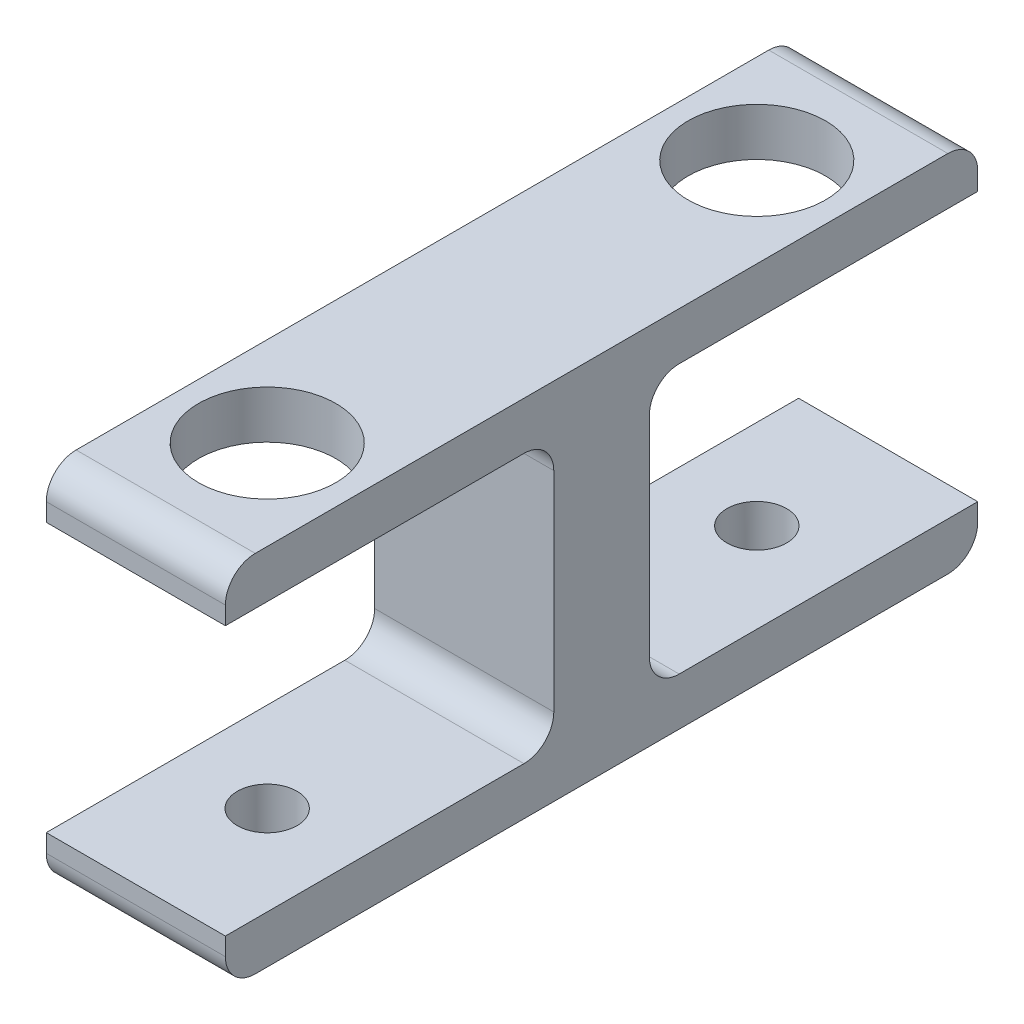
SolidWorks part; units mm, degrees
ref_plane "Front Plane" through (0, 0, 0) normal (0, 0, 1) x (1, 0, 0)
ref_plane "Top Plane" through (0, 0, 0) normal (0, 1, 0) x (1, 0, 0)
ref_plane "Right Plane" through (0, 0, 0) normal (1, 0, 0) x (0, 0, -1)
sketch "Sketch1" plane through (0, 0, 0) normal (1, 0, 0) x (0, 0, -1)
  line L0 (0, 0) -> (55, 0)
  line L1 (55, 0) -> (55, -45)
  line L2 (55, -45) -> (0, -45)
  line L3 (0, -45) -> (0, -53)
  line L4 (0, -53) -> (63, -53)
  line L5 (63, -53) -> (63, 8)
  line L6 (63, 8) -> (0, 8)
  line L7 (0, 8) -> (0, 0)
  dimension "D1" = 55
  dimension "D2" = 45
  dimension "D3" = 8
  dimension "D4" = 8
extrude "Boss-Extrude1" add sketch "Sketch1" along normal blind 30 contours L0 L1 L2 L3 L4 L5 L6 L7
sketch "Sketch2" plane through (0, 8, 0) normal (0, 1, 0) x (1, 0, 0)
  line L0 (30, 0) -> (0, 0) construction
  circle A0 centre (15, 22) radius 11.5
  point P2 (15, 0)
  dimension "D1" = 23
  dimension "D2" = 22
extrude "Cut-Extrude1" cut sketch "Sketch2" against normal up to next
sketch "Sketch3" plane through (0, -45, 0) normal (0, 1, 0) x (1, 0, 0)
  circle A0 centre (15, 22) radius 5
  circle A1 centre (15, 22) radius 11.5 construction
  dimension "D1" = 10
extrude "Cut-Extrude2" cut sketch "Sketch3" against normal up to next contours A0
fillet "Fillet2" radius 5 2 edges at (15, 0, -55) (15, -45, -55)
mirror "Mirror2" about plane through (30, -53, -63) normal (0, 0, 1) of "Fillet2", "Boss-Extrude1", "Cut-Extrude1", "Cut-Extrude2"
fillet "Fillet3" radius 5 4 edges at (15, -53, -126) (15, 8, -126) (15, -53, 0) (15, 8, 0)
